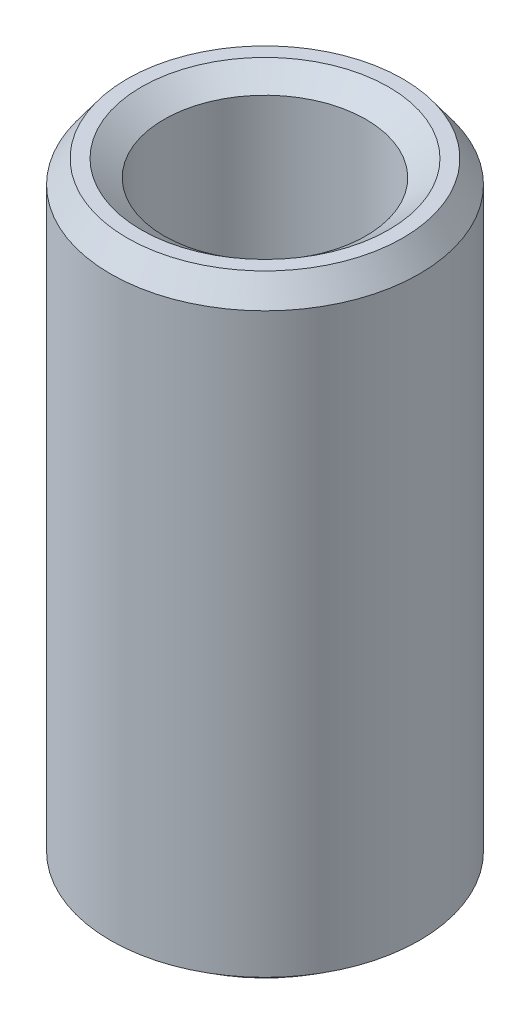
SolidWorks part; units mm, degrees
ref_plane "Front Plane" through (0, 0, 0) normal (0, 0, 1) x (1, 0, 0)
ref_plane "Top Plane" through (0, 0, 0) normal (0, 1, 0) x (1, 0, 0)
ref_plane "Right Plane" through (0, 0, 0) normal (1, 0, 0) x (0, 0, -1)
sketch "Sketch1" plane through (0, 0, 0) normal (0, 1, 0) x (1, 0, 0)
  circle A0 centre (0, 0) radius 7.5
  dimension "SLEEVE_OD" = 15
extrude "Boss-Extrude1" add sketch "Sketch1" along normal blind 29.9381
sketch "Sketch2" plane through (0, 0, 0) normal (0, 1, 0) x (1, 0, 0)
  circle A0 centre (0, 0) radius 4.9022
  dimension "BORE_D" = 9.8045
extrude "Cut-Extrude1" cut sketch "Sketch2" along normal through all
chamfer "Chamfer1" distance 1.1055 angle 36.166 4 edges at (0, 29.9381, 4.9022) (0, 0, 4.9022) (0, 0, 7.5) (0, 29.9381, 7.5) first distance on face at (0, 29.9381, 4.9022) first distance on face at (0, 0, 4.9022) first distance on face at (0, 29.9381, 7.5)
